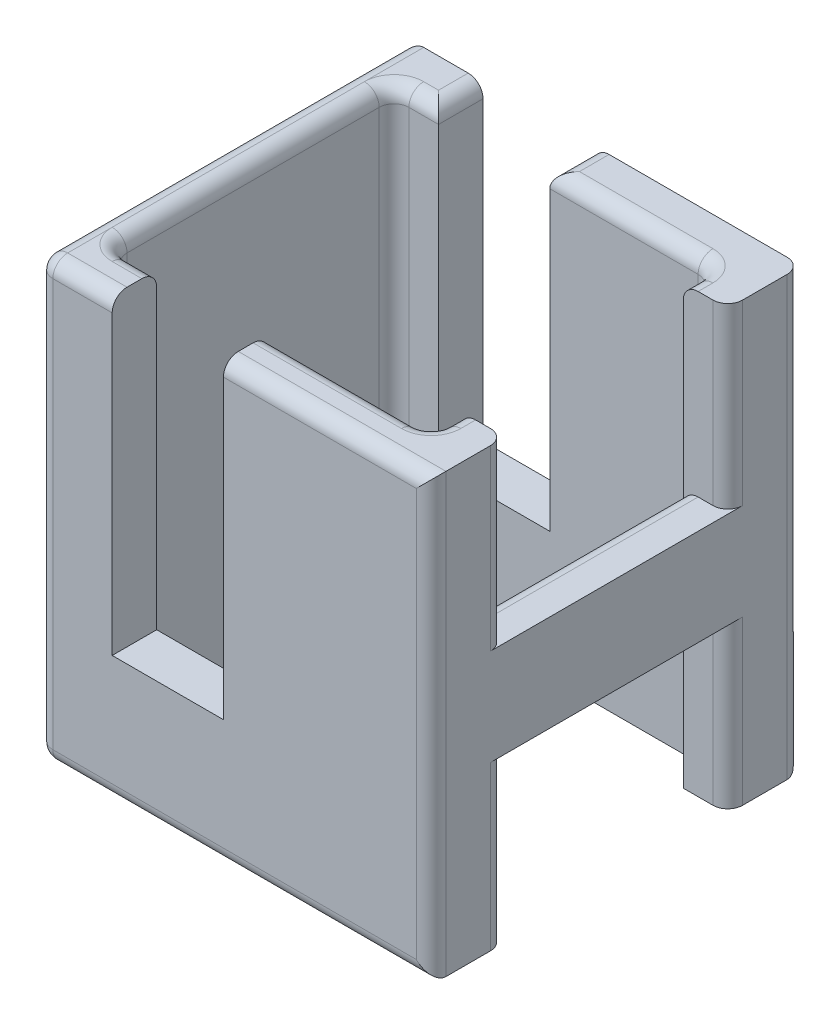
SolidWorks part; units mm, degrees
ref_plane "前视基准面" through (0, 0, 0) normal (0, 0, 1) x (1, 0, 0)
ref_plane "上视基准面" through (0, 0, 0) normal (0, 1, 0) x (1, 0, 0)
ref_plane "右视基准面" through (0, 0, 0) normal (1, 0, 0) x (0, 0, -1)
sketch "草图1" plane through (0, 0, 0) normal (0, 1, 0) x (1, 0, 0)
  line L0 (3, 0) -> (30.5, 0)
  line L1 (30.5, 0) -> (30.5, 25)
  line L2 (30.5, 25) -> (3, 25)
  line L5 (6, 3) -> (27.5, 3)
  line L6 (27.5, 3) -> (27.5, 22)
  line L7 (27.5, 22) -> (6, 22)
  line L8 (1, 25) -> (1, 0) construction
  line L10 (3, 25) -> (3, 0)
  line L11 (6, 22) -> (6, 3)
  line L12 (30.5, 25) -> (1, 25) construction
  line L13 (1, 0) -> (30.5, 0) construction
  line L15 (27.5, 22) -> (4, 22) construction
  line L16 (4, 22) -> (4, 3) construction
  line L17 (4, 3) -> (27.5, 3) construction
  dimension "D1" = 3
  dimension "D2" = 3
  dimension "D3" = 3
  dimension "D4" = 27.5
extrude "凸台-拉伸1" add sketch "草图1" along normal blind 36
sketch "草图3" plane through (30.5, 0, 0) normal (1, 0, 0) x (0, 0, -1)
  line L0 (5, 33) -> (5, 3)
  line L1 (5, 3) -> (20, 3)
  line L2 (20, 3) -> (20, 33)
  line L3 (20, 33) -> (5, 33)
  line L4 (0, 36) -> (25, 36) construction
  line L5 (0, 36) -> (0, 0) construction
  line L6 (25, 36) -> (25, 0) construction
  line L7 (0, 0) -> (25, 0) construction
  dimension "D1" = 3
  dimension "D2" = 5
  dimension "D3" = 5
  dimension "D4" = 3
extrude "切除-拉伸1" cut sketch "草图3" against normal up to surface (24.5 mm away) up to face at (6, 18, -12.5)
sketch "草图4" plane through (0, 0, -25) normal (0, 0, -1) x (-1, 0, 0)
  line L0 (-9, 36) -> (-9, 12)
  line L1 (-30.5, 36) -> (-3, 36) construction
  line L2 (-9, 12) -> (-16.5, 12)
  line L3 (-16.5, 12) -> (-16.5, 36)
  line L5 (-9, 36) -> (-16.5, 36)
  line L6 (-3, 36) -> (-3, 0) construction
  dimension "D1" = 6
  dimension "D2" = 24
  dimension "D3" = 7.5
extrude "切除-拉伸2" cut sketch "草图4" against normal up to next
sketch "草图5" plane through (30.5, 0, 0) normal (1, 0, 0) x (0, 0, -1)
  line L0 (0, 36) -> (25, 36)
  line L1 (25, 36) -> (25, 33)
  line L2 (25, 36) -> (25, 0) construction
  line L3 (25, 33) -> (0, 33)
  line L4 (0, 36) -> (0, 0) construction
  line L5 (0, 33) -> (0, 36)
  line L6 (25, 0) -> (25, 3.5)
  line L7 (25, 3.5) -> (0, 3.5)
  line L8 (0, 3.5) -> (0, 0)
  line L9 (0, 0) -> (25, 0)
  dimension "D1" = 3
  dimension "D2" = 3.5
extrude "切除-拉伸3" cut sketch "草图5" against normal through all
sketch "草图6" plane through (30.5, 0, 0) normal (1, 0, 0) x (0, 0, -1)
  line L0 (5, 21) -> (20, 21)
  line L1 (5, 33) -> (5, 3.5) construction
  line L2 (20, 3.5) -> (20, 33) construction
  line L3 (20, 21) -> (20, 14.5)
  line L4 (20, 14.5) -> (5, 14.5)
  line L5 (5, 14.5) -> (5, 21)
  line L7 (3, 33) -> (22, 33) construction
  line L8 (0, 33) -> (5, 33) construction
  dimension "D1" = 12
  dimension "D2" = 18.5
extrude "凸台-拉伸2" add sketch "草图6" against normal up to surface (3 mm away) up to face at (27.5, 18.25, -4)
fillet "圆角1" radius 1 27 edges at (7.5, 33, -22) (27.5, 33, -21) (27.5, 33, -4) (6, 33, -12.5) (22, 33, -22) (16.75, 33, -3) (27.5, 14.5, -12.5) (27.5, 21, -12.5) (30.5, 9, -5) (30.5, 9, -20) (30.5, 27, -20) (30.5, 27, -5) (27.5, 18.25, -3) (27.5, 18.25, -22) (6, 18.25, -22) (6, 18.25, -3) (3, 3.5, -12.5) (16.75, 3.5, 0) (16.75, 3.5, -25) (3, 33, -12.5) (16.75, 33, 0) (3, 18.25, 0) (3, 18.25, -25) (30.5, 18.25, -25) (30.5, 18.25, 0) (16.5, 33, -23.5) (9, 33, -23.5)
sketch "草图7" plane through (0, 33, 0) normal (0, 1, 0) x (1, 0, 0)
  line L0 (3, 25) -> (3, 0)
  line L1 (3, 0) -> (4, 0)
  line L2 (4, 0) -> (4, 1) construction
  line L3 (4, 0) -> (4, 25)
  line L4 (4, 25) -> (8, 25) construction
  line L5 (4, 25) -> (4, 1) construction
  line L6 (4, 25) -> (3, 25)
  arc A0 (3, 1) -> (4, 0) centre (4, 1) ccw construction
extrude "切除-拉伸5" cut sketch "草图7" against normal through all
fillet "圆角3" radius 1 7 edges at (4, 18.75, -25) (4, 3.7929, -24.7071) (4, 3.5, -12.5) (4, 3.7929, -0.2929) (4, 18.25, 0) (4, 32.7071, -0.2929) (4, 33, -13)
ref_plane "基准面1" through (0, 0, -12.5) normal (0, 0, -1) x (-1, 0, 0)
mirror "镜向1" about plane through (0, 0, -12.5) normal (0, 0, -1) of "切除-拉伸2"
